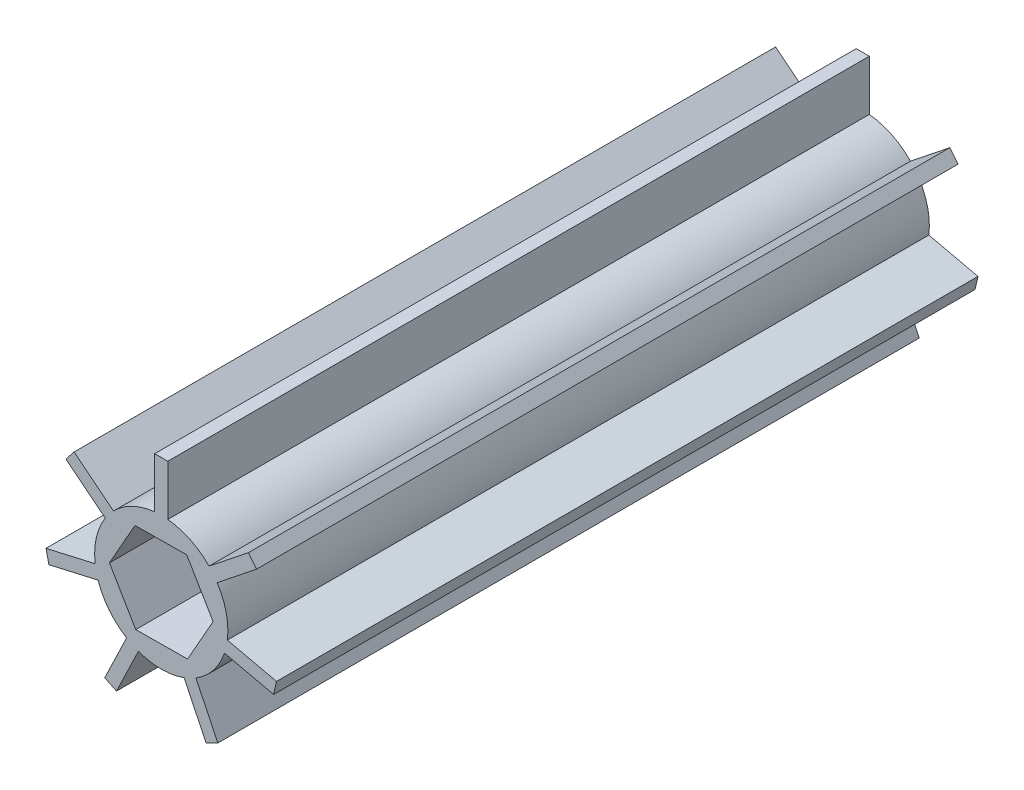
SolidWorks part; units mm, degrees
ref_plane "Front Plane" through (0, 0, 0) normal (0, 0, 1) x (1, 0, 0)
ref_plane "Top Plane" through (0, 0, 0) normal (0, 1, 0) x (1, 0, 0)
ref_plane "Right Plane" through (0, 0, 0) normal (1, 0, 0) x (0, 0, -1)
sketch "Sketch1" plane through (0, 0, 0) normal (0, 0, 1) x (1, 0, 0)
  circle A0 centre (0, 0) radius 12.7
  dimension "D1" = 25.4
sketch "Sketch6" plane through (0, 0, 0) normal (0, 0, 1) x (1, 0, 0)
  circle A0 centre (0, 0) radius 7.239
  dimension "D1" = 14.478
sketch "Sketch8" plane through (0, 0, 0) normal (0, 0, 1) x (1, 0, 0)
  line L1 (5.631, 0.0479) -> (2.7741, 4.9006)
  line L2 (2.7741, 4.9006) -> (-2.857, 4.8527)
  line L3 (-2.857, 4.8527) -> (-5.631, -0.0479)
  line L4 (-5.631, -0.0479) -> (-2.7741, -4.9006)
  line L5 (-2.7741, -4.9006) -> (2.857, -4.8527)
  line L6 (2.857, -4.8527) -> (5.631, 0.0479)
  circle A0 centre (0, 0) radius 4.8768 construction
  dimension "D1" = 4.8768
sketch "Sketch12" plane through (0, 0, 0) normal (0, 0, 1) x (1, 0, 0)
  line L0 (0, 0) -> (0.7112, 0)
  line L2 (-0.7112, 0) -> (-0.7112, 12.6801)
  line L3 (-0.7112, 12.6801) -> (0.7112, 12.6801)
  line L4 (0.7112, 0) -> (0.7112, 12.6801)
  line L5 (0, 0) -> (0.7112, 12.6801) construction
  line L6 (-0.7112, 12.6801) -> (0, 0) construction
  line L7 (0, 0) -> (-0.7112, 0)
  circle A0 centre (0, 0) radius 12.7 construction
  point P0 (0, 0)
  dimension "D1" = 1.4224
extrude "Boss-Extrude1" add sketch "Sketch12" against normal blind 76.2
extrude "Boss-Extrude2" add sketch "Sketch6" against normal blind 76.2 contours A0
ref_axis "Axis1" through (0, 0, -76.2) along (0, 0, 1)
pattern_circular "CirPattern1" count 7 over 360 about axis through (0, 0, -76.2) along (0, 0, 1) of "Boss-Extrude1"
extrude "Cut-Extrude5" cut sketch "Sketch8" against normal through all
